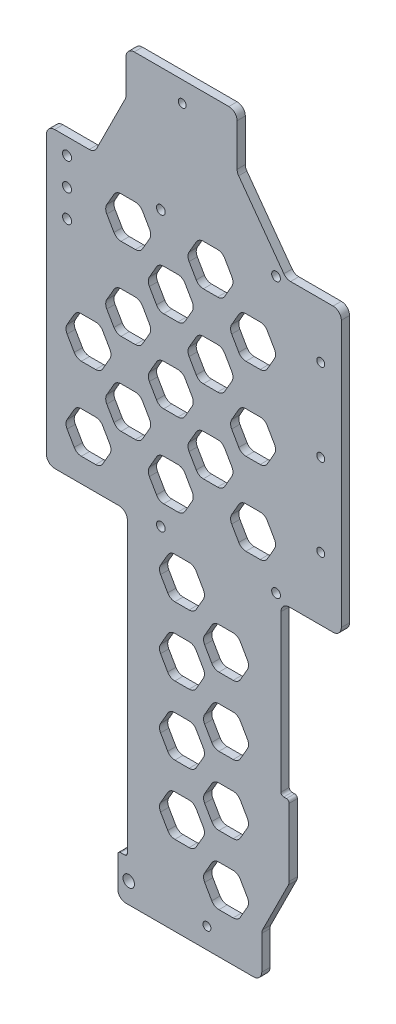
SolidWorks part; units mm, degrees
material "轻木"
ref_plane "前视基准面" through (0, 0, 0) normal (0, 0, 1) x (1, 0, 0)
ref_plane "上视基准面" through (0, 0, 0) normal (0, 1, 0) x (1, 0, 0)
ref_plane "右视基准面" through (0, 0, 0) normal (1, 0, 0) x (0, 0, -1)
other "Configuration Table"
sketch "草图1" plane through (0, 0, 0) normal (0, 0, 1) x (1, 0, 0)
  line L1 (260.5, -262.8015) -> (266.5, -262.8015)
  line L6 (266.5, -262.8015) -> (266.5, -247.8015)
  line L9 (266.5, -247.8015) -> (263, -247.8015) construction
  line L11 (260.5, -247.8015) -> (260.5, -188.5488) construction
  line L14 (307, -262.8015) -> (303.5, -262.8015)
  line L17 (303.5, -262.8015) -> (303.5, -247.8015)
  line L21 (303.5, -247.8015) -> (307, -247.8015)
  line L23 (307, -247.8015) -> (307, -188.5488)
  line L25 (266.5, -247.8015) -> (263, -247.8015)
  line L33 (263, -247.8015) -> (263, -138.5488)
  line L34 (263, -138.5488) -> (307, -138.5488)
  line L39 (219, 7.5) -> (267.5, 7.5) construction
  line L40 (219, 7.5) -> (219, -4.5) construction
  line L41 (267.5, 7.5) -> (267.5, -7.5) construction
  line L42 (570, -7.5) -> (0, -7.5) construction
  line L43 (267.5, -7.5) -> (277.5, -27.5) construction
  line L44 (277.5, -247.8015) -> (277.5, -7.5015) construction
  line L45 (277.5, -27.5) -> (292.5, -27.5) construction
  line L46 (292.5, -247.8015) -> (292.5, -7.5015) construction
  line L47 (292.5, -27.5) -> (302.5, -7.5) construction
  line L48 (302.5, -7.5) -> (302.5, 7.5) construction
  line L49 (570, 7.5) -> (0, 7.5) construction
  line L50 (302.5, 7.5) -> (351, 7.5) construction
  line L51 (351, 7.5) -> (351, -10.5) construction
  line L52 (351, -10.5) -> (367, -32.5) construction
  line L54 (367, -32.5) -> (367, -13.5) construction
  line L55 (373, -32.5) -> (367, -32.5) construction
  line L56 (367, -32.5) -> (385, -32.5) construction
  line L57 (388, -32.5) -> (382, -32.5) construction
  line L58 (385, -32.5) -> (385, -143.5) construction
  line L59 (385, -143.5) -> (367, -143.5) construction
  line L60 (367, -143.5) -> (367, -196.5) construction
  line L61 (367, -196.5) -> (370, -196.5) construction
  line L62 (370, -196.5) -> (370, -227.8015) construction
  line L63 (370, -7.5015) -> (370, -247.8015) construction
  line L64 (370, -227.8015) -> (360, -247.8015) construction
  line L65 (465, -247.8015) -> (105, -247.8015) construction
  line L66 (360, -247.8015) -> (360, -262.8015) construction
  line L67 (303, -262.8015) -> (303, -192.5488) construction
  line L68 (303, -192.5488) -> (264.5, -192.5488) construction
  line L69 (264.5, -192.5488) -> (264.5, -262.8015) construction
  line L70 (465, -262.8015) -> (105, -262.8015) construction
  line L71 (360, -262.8015) -> (303, -262.8015) construction
  line L72 (360.5279, -246.7458) -> (368.618, -230.5654) construction
  line L73 (264.5, -262.8015) -> (210, -262.8015) construction
  line L74 (210, -262.8015) -> (210, -247.8015) construction
  line L75 (210, -247.8015) -> (200, -227.8015) construction
  line L76 (200, -7.5015) -> (200, -247.8015) construction
  line L77 (200, -227.8015) -> (200, -196.5) construction
  line L78 (200, -196.5) -> (203, -196.5) construction
  line L79 (203, -196.5) -> (203, -143.5) construction
  line L80 (203, -143.5) -> (185, -143.5) construction
  line L81 (188, -143.5) -> (182, -143.5) construction
  line L82 (185, -143.5) -> (185, -32.5) construction
  line L83 (185, -7.5015) -> (185, -247.8015) construction
  line L84 (185, -32.5) -> (203, -32.5) construction
  line L85 (203, -32.5) -> (219, -10.5) construction
  line L86 (219, -10.5) -> (219, 7.5) construction
  line L87 (276.118, -24.7361) -> (268.0279, -8.5557) construction
  line L88 (301.9721, -8.5557) -> (293.882, -24.7361) construction
  line L89 (201.382, -230.5654) -> (209.4721, -246.7458) construction
  line L90 (223, -11.8007) -> (223, 3.5) construction
  line L91 (223, 3.5) -> (263.5, 3.5) construction
  line L92 (263.5, 3.5) -> (263.5, -8.4443) construction
  line L93 (263.5, -8.4443) -> (275.0279, -31.5) construction
  line L94 (275.0279, -31.5) -> (294.9721, -31.5) construction
  line L95 (294.9721, -31.5) -> (306.5, -8.4443) construction
  line L96 (306.5, -8.4443) -> (306.5, 3.5) construction
  line L97 (306.5, 3.5) -> (347, 3.5) construction
  line L98 (347, 3.5) -> (347, -11.8007) construction
  line L99 (347, -11.8007) -> (364.9631, -36.5) construction
  line L100 (364.9631, -36.5) -> (381, -36.5) construction
  line L101 (381, -36.5) -> (381, -139.5) construction
  line L102 (381, -139.5) -> (363, -139.5) construction
  line L103 (363, -139.5) -> (363, -200.5) construction
  line L104 (363, -200.5) -> (366, -200.5) construction
  line L105 (366, -200.5) -> (366, -226.8572) construction
  line L106 (366, -226.8572) -> (356, -246.8572) construction
  line L107 (356, -246.8572) -> (356, -258.8015) construction
  line L108 (356, -258.8015) -> (307, -258.8015) construction
  line L109 (307, -258.8015) -> (307, -188.5488) construction
  line L110 (307, -188.5488) -> (260.5, -188.5488) construction
  line L111 (260.5, -188.5488) -> (260.5, -258.8015) construction
  line L112 (260.5, -258.8015) -> (214, -258.8015) construction
  line L113 (214, -258.8015) -> (214, -246.8572) construction
  line L114 (214, -246.8572) -> (204, -226.8572) construction
  line L115 (204, -226.8572) -> (204, -200.5) construction
  line L116 (204, -200.5) -> (207, -200.5) construction
  line L117 (207, -200.5) -> (207, -139.5) construction
  line L118 (207, -139.5) -> (189, -139.5) construction
  line L119 (189, -139.5) -> (189, -36.5) construction
  line L120 (189, -36.5) -> (205.0369, -36.5) construction
  line L121 (205.0369, -36.5) -> (223, -11.8007) construction
  line L122 (223, -11.8007) -> (223, 7.5)
  line L123 (263.5, -8.4443) -> (263.5, 7.5)
  line L124 (263.5, 7.5) -> (223, 7.5)
  line L125 (223, -11.8007) -> (205.0369, -36.5)
  line L126 (205.0369, -36.5) -> (185, -36.5)
  line L127 (185, -36.5) -> (185, -139.5)
  line L128 (185, -139.5) -> (207, -139.5)
  line L129 (207, -139.5) -> (207, -200.5)
  line L130 (204, -200.5) -> (204, -226.8572)
  line L131 (204, -226.8572) -> (214, -246.8572)
  line L132 (204, -200.5) -> (207, -200.5)
  line L133 (214, -246.8572) -> (214, -262.8015)
  line L134 (214, -262.8015) -> (260.5, -262.8015)
  line L135 (260.5, -262.8015) -> (260.5, -188.5488) construction
  line L137 (307, -188.5488) -> (307, -262.8015) construction
  line L138 (307, -262.8015) -> (356, -262.8015)
  line L139 (356, -262.8015) -> (356, -246.8572)
  line L140 (356, -246.8572) -> (366, -226.8572)
  line L141 (366, -226.8572) -> (366, -200.5)
  line L142 (366, -200.5) -> (363, -200.5)
  line L143 (363, -200.5) -> (363, -139.5)
  line L144 (363, -139.5) -> (385, -139.5)
  line L145 (385, -139.5) -> (385, -36.5)
  line L146 (385, -36.5) -> (364.9631, -36.5)
  line L147 (364.9631, -36.5) -> (347, -11.8007)
  line L151 (306.5, -8.4443) -> (294.9721, -31.5)
  line L152 (294.9721, -31.5) -> (275.0279, -31.5)
  line L153 (275.0279, -31.5) -> (263.5, -8.4443)
  line L154 (306.5, -8.4443) -> (306.5, 7.5)
  line L155 (306.5, 7.5) -> (347, 7.5)
  line L156 (347, 7.5) -> (347, -11.8007)
  line L157 (260.5, -188.5488) -> (260.5, -138.5488) construction
  line L158 (260.5, -138.5488) -> (307, -138.5488) construction
  line L159 (307, -138.5488) -> (307, -188.5488)
  circle A0 centre (262.5, -255.3015) radius 2.1
  circle A1 centre (307.5, -255.3015) radius 2.1
  dimension "D7" = 7.5
  dimension "D8" = 7.5
  dimension "D9" = 4
  dimension "D11" = 4.2
  dimension "D12" = 4.2
  dimension "D2" = 50
  dimension "D3" = 15
  dimension "D4" = 15
  dimension "D5" = 6
  dimension "D6" = 3.5
  dimension "D10" = 0.5
  dimension "D13" = 3.5
  dimension "D1" = 4
extrude "凸台-拉伸1" add sketch "草图1" along normal blind 3
sketch "草图2" plane through (0, 0, 3) normal (0, 0, 1) x (1, 0, 0)
  line L0 (192.5, -27.4253) -> (192.5, -166.3023) construction
  line L1 (209.9028, 0) -> (386.3764, 0) construction
  line L3 (194.5573, -255.3015) -> (369.9095, -255.3015) construction
  line L4 (185, -36.5) -> (185, -139.5) construction
  line L5 (285, 13.2404) -> (285, -276.9819) construction
  line L6 (385, -139.5) -> (385, -36.5) construction
  line L7 (263.5, 7.5) -> (223, 7.5) construction
  line L8 (214, -262.8015) -> (266.5, -262.8015) construction
  line L9 (223, 7.5) -> (223, -11.8007) construction
  line L10 (205.0369, -36.5) -> (185, -36.5) construction
  line L11 (214, -246.8572) -> (214, -262.8015) construction
  circle A0 centre (192.5, -56.5) radius 1.45
  circle A1 centre (192.5, -86.5) radius 1.45
  circle A2 centre (192.5, -116.5) radius 1.45
  circle A3 centre (243, 0) radius 1.45
  circle A4 centre (234, -255.3015) radius 1.45
  circle A5 centre (377.5, -56.5) radius 1.45
  circle A6 centre (327, 0) radius 1.45
  circle A7 centre (377.5, -86.5) radius 1.45
  circle A8 centre (377.5, -116.5) radius 1.45
  circle A9 centre (336, -255.3015) radius 1.45
  dimension "D5" = 20
  dimension "D6" = 30
  dimension "D7" = 30
  dimension "D8" = 2.9
  dimension "D1" = 7.5
  dimension "D2" = 7.5
  dimension "D3" = 7.5
  dimension "D4" = 20
  dimension "D9" = 20
extrude "切除-拉伸1" cut sketch "草图2" against normal through all
fillet "圆角2" radius 3 28 edges at (214, -262.8015, 1.5) (214, -246.8572, 1.5) (204, -226.8572, 1.5) (207, -139.5, 1.5) (185, -139.5, 1.5) (185, -36.5, 1.5) (205.0369, -36.5, 1.5) (223, -11.8007, 1.5) (223, 7.5, 1.5) (263.5, 7.5, 1.5) (263.5, -8.4443, 1.5) (275.0279, -31.5, 1.5) (294.9721, -31.5, 1.5) (306.5, -8.4443, 1.5) (306.5, 7.5, 1.5) (347, 7.5, 1.5) (385, -36.5, 1.5) (385, -139.5, 1.5) (363, -139.5, 1.5) (366, -226.8572, 1.5) (356, -246.8572, 1.5) (356, -262.8015, 1.5) (347, -11.8007, 1.5) (364.9631, -36.5, 1.5) (303.5, -262.8015, 1.5) (266.5, -262.8015, 1.5) (307, -138.5488, 1.5) (263, -138.5488, 1.5)
fillet "圆角4" radius 1 8 edges at (204, -200.5, 1.5) (207, -200.5, 1.5) (366, -200.5, 1.5) (363, -200.5, 1.5) (307, -247.8015, 1.5) (303.5, -247.8015, 1.5) (263, -247.8015, 1.5) (266.5, -247.8015, 1.5)
sketch "草图3" plane through (0, 0, 3) normal (0, 0, 1) x (1, 0, 0)
  circle A0 centre (319.2014, -37.5) radius 1.6 construction
  circle A1 centre (361.2014, -37.5) radius 1.6 construction
  circle A2 centre (319.2014, -37.5) radius 1.6
  circle A3 centre (361.2014, -37.5) radius 1.6
  circle A4 centre (361.2014, -137.5) radius 1.6 construction
  circle A5 centre (319.2014, -137.5) radius 1.6 construction
  circle A6 centre (361.2014, -137.5) radius 1.6
  circle A7 centre (319.2014, -137.5) radius 1.6
  circle A8 centre (285, -37.5) radius 1.65 construction
  circle A9 centre (285, -47.5) radius 1.65 construction
  circle A10 centre (285, -57.5) radius 1.65 construction
  circle A11 centre (285, -37.5) radius 1.65
  circle A12 centre (285, -47.5) radius 1.65
  circle A13 centre (285, -57.5) radius 1.65
extrude "切除-拉伸2" cut sketch "草图3" against normal through all
sketch "草图4" plane through (0, 0, 3) normal (0, 0, 1) x (1, 0, 0)
  line L0 (255.9607, -47.2012) -> (251.6306, -39.7012)
  line L1 (225.9607, -47.2012) -> (221.6306, -39.7012)
  line L2 (221.6306, -39.7012) -> (212.9703, -39.7012)
  line L3 (212.9703, -39.7012) -> (208.6402, -47.2012)
  line L4 (208.6402, -47.2012) -> (212.9703, -54.7012)
  line L5 (212.9703, -54.7012) -> (221.6306, -54.7012)
  line L6 (221.6306, -54.7012) -> (225.9607, -47.2012)
  line L7 (241.4816, -62.3181) -> (237.1515, -54.8181)
  line L8 (237.1515, -54.8181) -> (228.4912, -54.8181)
  line L9 (228.4912, -54.8181) -> (224.1611, -62.3181)
  line L10 (224.1611, -62.3181) -> (228.4912, -69.8181)
  line L11 (228.4912, -69.8181) -> (237.1515, -69.8181)
  line L12 (237.1515, -69.8181) -> (241.4816, -62.3181)
  line L13 (251.6306, -39.7012) -> (242.9703, -39.7012)
  line L14 (242.9703, -39.7012) -> (238.6402, -47.2012)
  line L15 (238.6402, -47.2012) -> (242.9703, -54.7012)
  line L16 (242.9703, -54.7012) -> (251.6306, -54.7012)
  line L17 (251.6306, -54.7012) -> (255.9607, -47.2012)
  line L18 (271.4816, -62.3181) -> (267.1515, -54.8181)
  line L19 (267.1515, -54.8181) -> (258.4912, -54.8181)
  line L20 (258.4912, -54.8181) -> (254.1611, -62.3181)
  line L21 (254.1611, -62.3181) -> (258.4912, -69.8181)
  line L22 (258.4912, -69.8181) -> (267.1515, -69.8181)
  line L23 (267.1515, -69.8181) -> (271.4816, -62.3181)
  line L36 (315.9607, -47.2012) -> (311.6306, -39.7012)
  line L37 (311.6306, -39.7012) -> (302.9703, -39.7012)
  line L38 (302.9703, -39.7012) -> (298.6402, -47.2012)
  line L39 (298.6402, -47.2012) -> (302.9703, -54.7012)
  line L40 (302.9703, -54.7012) -> (311.6306, -54.7012)
  line L41 (311.6306, -54.7012) -> (315.9607, -47.2012)
  line L42 (331.4816, -62.3181) -> (327.1515, -54.8181)
  line L43 (327.1515, -54.8181) -> (318.4912, -54.8181)
  line L44 (318.4912, -54.8181) -> (314.1611, -62.3181)
  line L45 (314.1611, -62.3181) -> (318.4912, -69.8181)
  line L46 (318.4912, -69.8181) -> (327.1515, -69.8181)
  line L47 (327.1515, -69.8181) -> (331.4816, -62.3181)
  line L48 (345.9607, -47.2012) -> (341.6306, -39.7012)
  line L49 (341.6306, -39.7012) -> (332.9703, -39.7012)
  line L50 (332.9703, -39.7012) -> (328.6402, -47.2012)
  line L51 (328.6402, -47.2012) -> (332.9703, -54.7012)
  line L52 (332.9703, -54.7012) -> (341.6306, -54.7012)
  line L53 (341.6306, -54.7012) -> (345.9607, -47.2012)
  line L54 (361.4816, -62.3181) -> (357.1515, -54.8181)
  line L55 (357.1515, -54.8181) -> (348.4912, -54.8181)
  line L56 (348.4912, -54.8181) -> (344.1611, -62.3181)
  line L57 (344.1611, -62.3181) -> (348.4912, -69.8181)
  line L58 (348.4912, -69.8181) -> (357.1515, -69.8181)
  line L59 (357.1515, -69.8181) -> (361.4816, -62.3181)
  line L60 (255.9607, -77.2012) -> (251.6306, -69.7012)
  line L61 (251.6306, -69.7012) -> (242.9703, -69.7012)
  line L62 (242.9703, -69.7012) -> (238.6402, -77.2012)
  line L63 (238.6402, -77.2012) -> (242.9703, -84.7012)
  line L64 (242.9703, -84.7012) -> (251.6306, -84.7012)
  line L65 (251.6306, -84.7012) -> (255.9607, -77.2012)
  line L66 (271.4816, -92.3181) -> (267.1515, -84.8181)
  line L67 (267.1515, -84.8181) -> (258.4912, -84.8181)
  line L68 (258.4912, -84.8181) -> (254.1611, -92.3181)
  line L69 (254.1611, -92.3181) -> (258.4912, -99.8181)
  line L70 (258.4912, -99.8181) -> (267.1515, -99.8181)
  line L71 (267.1515, -99.8181) -> (271.4816, -92.3181)
  line L78 (301.4816, -92.3181) -> (297.1515, -84.8181)
  line L79 (297.1515, -84.8181) -> (288.4912, -84.8181)
  line L80 (288.4912, -84.8181) -> (284.1611, -92.3181)
  line L81 (284.1611, -92.3181) -> (288.4912, -99.8181)
  line L82 (288.4912, -99.8181) -> (297.1515, -99.8181)
  line L83 (297.1515, -99.8181) -> (301.4816, -92.3181)
  line L84 (315.9607, -77.2012) -> (311.6306, -69.7012)
  line L85 (311.6306, -69.7012) -> (302.9703, -69.7012)
  line L86 (302.9703, -69.7012) -> (298.6402, -77.2012)
  line L87 (298.6402, -77.2012) -> (302.9703, -84.7012)
  line L88 (302.9703, -84.7012) -> (311.6306, -84.7012)
  line L89 (311.6306, -84.7012) -> (315.9607, -77.2012)
  line L90 (331.4816, -92.3181) -> (327.1515, -84.8181)
  line L91 (327.1515, -84.8181) -> (318.4912, -84.8181)
  line L92 (318.4912, -84.8181) -> (314.1611, -92.3181)
  line L93 (314.1611, -92.3181) -> (318.4912, -99.8181)
  line L94 (318.4912, -99.8181) -> (327.1515, -99.8181)
  line L95 (327.1515, -99.8181) -> (331.4816, -92.3181)
  line L96 (345.9607, -77.2012) -> (341.6306, -69.7012)
  line L97 (341.6306, -69.7012) -> (332.9703, -69.7012)
  line L98 (332.9703, -69.7012) -> (328.6402, -77.2012)
  line L99 (328.6402, -77.2012) -> (332.9703, -84.7012)
  line L100 (332.9703, -84.7012) -> (341.6306, -84.7012)
  line L101 (341.6306, -84.7012) -> (345.9607, -77.2012)
  line L102 (361.4816, -92.3181) -> (357.1515, -84.8181)
  line L103 (357.1515, -84.8181) -> (348.4912, -84.8181)
  line L104 (348.4912, -84.8181) -> (344.1611, -92.3181)
  line L105 (344.1611, -92.3181) -> (348.4912, -99.8181)
  line L106 (348.4912, -99.8181) -> (357.1515, -99.8181)
  line L107 (357.1515, -99.8181) -> (361.4816, -92.3181)
  line L108 (255.9607, -107.2012) -> (251.6306, -99.7012)
  line L109 (251.6306, -99.7012) -> (242.9703, -99.7012)
  line L110 (242.9703, -99.7012) -> (238.6402, -107.2012)
  line L111 (238.6402, -107.2012) -> (242.9703, -114.7012)
  line L112 (242.9703, -114.7012) -> (251.6306, -114.7012)
  line L113 (251.6306, -114.7012) -> (255.9607, -107.2012)
  line L114 (271.4816, -122.3181) -> (267.1515, -114.8181)
  line L115 (267.1515, -114.8181) -> (258.4912, -114.8181)
  line L116 (258.4912, -114.8181) -> (254.1611, -122.3181)
  line L117 (254.1611, -122.3181) -> (258.4912, -129.8181)
  line L118 (258.4912, -129.8181) -> (267.1515, -129.8181)
  line L119 (267.1515, -129.8181) -> (271.4816, -122.3181)
  line L126 (301.4816, -122.3181) -> (297.1515, -114.8181)
  line L127 (297.1515, -114.8181) -> (288.4912, -114.8181)
  line L128 (288.4912, -114.8181) -> (284.1611, -122.3181)
  line L129 (284.1611, -122.3181) -> (288.4912, -129.8181)
  line L130 (288.4912, -129.8181) -> (297.1515, -129.8181)
  line L131 (297.1515, -129.8181) -> (301.4816, -122.3181)
  line L132 (315.9607, -107.2012) -> (311.6306, -99.7012)
  line L133 (311.6306, -99.7012) -> (302.9703, -99.7012)
  line L134 (302.9703, -99.7012) -> (298.6402, -107.2012)
  line L135 (298.6402, -107.2012) -> (302.9703, -114.7012)
  line L136 (302.9703, -114.7012) -> (311.6306, -114.7012)
  line L137 (311.6306, -114.7012) -> (315.9607, -107.2012)
  line L138 (331.4816, -122.3181) -> (327.1515, -114.8181)
  line L139 (327.1515, -114.8181) -> (318.4912, -114.8181)
  line L140 (318.4912, -114.8181) -> (314.1611, -122.3181)
  line L141 (314.1611, -122.3181) -> (318.4912, -129.8181)
  line L142 (318.4912, -129.8181) -> (327.1515, -129.8181)
  line L143 (327.1515, -129.8181) -> (331.4816, -122.3181)
  line L144 (345.9607, -107.2012) -> (341.6306, -99.7012)
  line L145 (341.6306, -99.7012) -> (332.9703, -99.7012)
  line L146 (332.9703, -99.7012) -> (328.6402, -107.2012)
  line L147 (328.6402, -107.2012) -> (332.9703, -114.7012)
  line L148 (332.9703, -114.7012) -> (341.6306, -114.7012)
  line L149 (341.6306, -114.7012) -> (345.9607, -107.2012)
  line L150 (361.4816, -122.3181) -> (357.1515, -114.8181)
  line L151 (357.1515, -114.8181) -> (348.4912, -114.8181)
  line L152 (348.4912, -114.8181) -> (344.1611, -122.3181)
  line L153 (344.1611, -122.3181) -> (348.4912, -129.8181)
  line L154 (348.4912, -129.8181) -> (357.1515, -129.8181)
  line L155 (357.1515, -129.8181) -> (361.4816, -122.3181)
  line L156 (225.9607, -77.2012) -> (221.6306, -69.7012)
  line L157 (221.6306, -69.7012) -> (212.9703, -69.7012)
  line L158 (212.9703, -69.7012) -> (208.6402, -77.2012)
  line L159 (208.6402, -77.2012) -> (212.9703, -84.7012)
  line L160 (212.9703, -84.7012) -> (221.6306, -84.7012)
  line L161 (221.6306, -84.7012) -> (225.9607, -77.2012)
  line L162 (241.4816, -92.3181) -> (237.1515, -84.8181)
  line L163 (237.1515, -84.8181) -> (228.4912, -84.8181)
  line L164 (228.4912, -84.8181) -> (224.1611, -92.3181)
  line L165 (224.1611, -92.3181) -> (228.4912, -99.8181)
  line L166 (228.4912, -99.8181) -> (237.1515, -99.8181)
  line L167 (237.1515, -99.8181) -> (241.4816, -92.3181)
  line L168 (225.9607, -107.2012) -> (221.6306, -99.7012)
  line L169 (221.6306, -99.7012) -> (212.9703, -99.7012)
  line L170 (212.9703, -99.7012) -> (208.6402, -107.2012)
  line L171 (208.6402, -107.2012) -> (212.9703, -114.7012)
  line L172 (212.9703, -114.7012) -> (221.6306, -114.7012)
  line L173 (221.6306, -114.7012) -> (225.9607, -107.2012)
  line L174 (241.4816, -122.3181) -> (237.1515, -114.8181)
  line L175 (237.1515, -114.8181) -> (228.4912, -114.8181)
  line L176 (228.4912, -114.8181) -> (224.1611, -122.3181)
  line L177 (224.1611, -122.3181) -> (228.4912, -129.8181)
  line L178 (228.4912, -129.8181) -> (237.1515, -129.8181)
  line L179 (237.1515, -129.8181) -> (241.4816, -122.3181)
  line L180 (335.5655, -151.2096) -> (331.2354, -143.7096)
  line L181 (235.5655, -151.2096) -> (231.2354, -143.7096)
  line L182 (231.2354, -143.7096) -> (222.5752, -143.7096)
  line L183 (222.5752, -143.7096) -> (218.245, -151.2096)
  line L184 (218.245, -151.2096) -> (222.5752, -158.7096)
  line L185 (222.5752, -158.7096) -> (231.2354, -158.7096)
  line L186 (231.2354, -158.7096) -> (235.5655, -151.2096)
  line L187 (251.6306, -165.3842) -> (247.3004, -157.8842)
  line L188 (247.3004, -157.8842) -> (238.6402, -157.8842)
  line L189 (238.6402, -157.8842) -> (234.3101, -165.3842)
  line L190 (234.3101, -165.3842) -> (238.6402, -172.8842)
  line L191 (238.6402, -172.8842) -> (247.3004, -172.8842)
  line L192 (247.3004, -172.8842) -> (251.6306, -165.3842)
  line L193 (331.2354, -143.7096) -> (322.5752, -143.7096)
  line L194 (322.5752, -143.7096) -> (318.245, -151.2096)
  line L195 (318.245, -151.2096) -> (322.5752, -158.7096)
  line L196 (322.5752, -158.7096) -> (331.2354, -158.7096)
  line L197 (331.2354, -158.7096) -> (335.5655, -151.2096)
  line L198 (351.6306, -165.3842) -> (347.3004, -157.8842)
  line L199 (347.3004, -157.8842) -> (338.6402, -157.8842)
  line L200 (338.6402, -157.8842) -> (334.3101, -165.3842)
  line L201 (334.3101, -165.3842) -> (338.6402, -172.8842)
  line L202 (338.6402, -172.8842) -> (347.3004, -172.8842)
  line L203 (347.3004, -172.8842) -> (351.6306, -165.3842)
  line L204 (335.5655, -176.2096) -> (331.2354, -168.7096)
  line L205 (331.2354, -168.7096) -> (322.5752, -168.7096)
  line L206 (322.5752, -168.7096) -> (318.245, -176.2096)
  line L207 (318.245, -176.2096) -> (322.5752, -183.7096)
  line L208 (322.5752, -183.7096) -> (331.2354, -183.7096)
  line L209 (331.2354, -183.7096) -> (335.5655, -176.2096)
  line L210 (351.6306, -190.3842) -> (347.3004, -182.8842)
  line L211 (347.3004, -182.8842) -> (338.6402, -182.8842)
  line L212 (338.6402, -182.8842) -> (334.3101, -190.3842)
  line L213 (334.3101, -190.3842) -> (338.6402, -197.8842)
  line L214 (338.6402, -197.8842) -> (347.3004, -197.8842)
  line L215 (347.3004, -197.8842) -> (351.6306, -190.3842)
  line L216 (335.5655, -201.2096) -> (331.2354, -193.7096)
  line L217 (331.2354, -193.7096) -> (322.5752, -193.7096)
  line L218 (322.5752, -193.7096) -> (318.245, -201.2096)
  line L219 (318.245, -201.2096) -> (322.5752, -208.7096)
  line L220 (322.5752, -208.7096) -> (331.2354, -208.7096)
  line L221 (331.2354, -208.7096) -> (335.5655, -201.2096)
  line L222 (351.6306, -215.3842) -> (347.3004, -207.8842)
  line L223 (347.3004, -207.8842) -> (338.6402, -207.8842)
  line L224 (338.6402, -207.8842) -> (334.3101, -215.3842)
  line L225 (334.3101, -215.3842) -> (338.6402, -222.8842)
  line L226 (338.6402, -222.8842) -> (347.3004, -222.8842)
  line L227 (347.3004, -222.8842) -> (351.6306, -215.3842)
  line L228 (335.5655, -226.2096) -> (331.2354, -218.7096)
  line L229 (331.2354, -218.7096) -> (322.5752, -218.7096)
  line L230 (322.5752, -218.7096) -> (318.245, -226.2096)
  line L231 (318.245, -226.2096) -> (322.5752, -233.7096)
  line L232 (322.5752, -233.7096) -> (331.2354, -233.7096)
  line L233 (331.2354, -233.7096) -> (335.5655, -226.2096)
  line L234 (351.6306, -240.3842) -> (347.3004, -232.8842)
  line L235 (347.3004, -232.8842) -> (338.6402, -232.8842)
  line L236 (338.6402, -232.8842) -> (334.3101, -240.3842)
  line L237 (334.3101, -240.3842) -> (338.6402, -247.8842)
  line L238 (338.6402, -247.8842) -> (347.3004, -247.8842)
  line L239 (347.3004, -247.8842) -> (351.6306, -240.3842)
  line L240 (235.5655, -176.2096) -> (231.2354, -168.7096)
  line L241 (231.2354, -168.7096) -> (222.5752, -168.7096)
  line L242 (222.5752, -168.7096) -> (218.245, -176.2096)
  line L243 (218.245, -176.2096) -> (222.5752, -183.7096)
  line L244 (222.5752, -183.7096) -> (231.2354, -183.7096)
  line L245 (231.2354, -183.7096) -> (235.5655, -176.2096)
  line L246 (251.6306, -190.3842) -> (247.3004, -182.8842)
  line L247 (247.3004, -182.8842) -> (238.6402, -182.8842)
  line L248 (238.6402, -182.8842) -> (234.3101, -190.3842)
  line L249 (234.3101, -190.3842) -> (238.6402, -197.8842)
  line L250 (238.6402, -197.8842) -> (247.3004, -197.8842)
  line L251 (247.3004, -197.8842) -> (251.6306, -190.3842)
  line L252 (235.5655, -201.2096) -> (231.2354, -193.7096)
  line L253 (231.2354, -193.7096) -> (222.5752, -193.7096)
  line L254 (222.5752, -193.7096) -> (218.245, -201.2096)
  line L255 (218.245, -201.2096) -> (222.5752, -208.7096)
  line L256 (222.5752, -208.7096) -> (231.2354, -208.7096)
  line L257 (231.2354, -208.7096) -> (235.5655, -201.2096)
  line L258 (251.6306, -215.3842) -> (247.3004, -207.8842)
  line L259 (247.3004, -207.8842) -> (238.6402, -207.8842)
  line L260 (238.6402, -207.8842) -> (234.3101, -215.3842)
  line L261 (234.3101, -215.3842) -> (238.6402, -222.8842)
  line L262 (238.6402, -222.8842) -> (247.3004, -222.8842)
  line L263 (247.3004, -222.8842) -> (251.6306, -215.3842)
  line L264 (235.5655, -226.2096) -> (231.2354, -218.7096)
  line L265 (231.2354, -218.7096) -> (222.5752, -218.7096)
  line L266 (222.5752, -218.7096) -> (218.245, -226.2096)
  line L267 (218.245, -226.2096) -> (222.5752, -233.7096)
  line L268 (222.5752, -233.7096) -> (231.2354, -233.7096)
  line L269 (231.2354, -233.7096) -> (235.5655, -226.2096)
  line L270 (251.6306, -240.3842) -> (247.3004, -232.8842)
  line L271 (247.3004, -232.8842) -> (238.6402, -232.8842)
  line L272 (238.6402, -232.8842) -> (234.3101, -240.3842)
  line L273 (234.3101, -240.3842) -> (238.6402, -247.8842)
  line L274 (238.6402, -247.8842) -> (247.3004, -247.8842)
  line L275 (247.3004, -247.8842) -> (251.6306, -240.3842)
  line L276 (272.9703, -39.7012) -> (268.6402, -47.2012) [skipped]
  line L277 (272.9703, -54.7012) -> (281.6306, -54.7012) [skipped]
  line L278 (268.6402, -47.2012) -> (272.9703, -54.7012) [skipped]
  line L279 (281.6306, -54.7012) -> (285.9607, -47.2012) [skipped]
  line L280 (285.9607, -47.2012) -> (281.6306, -39.7012) [skipped]
  line L281 (281.6306, -39.7012) -> (272.9703, -39.7012) [skipped]
  line L282 (288.4912, -54.8181) -> (284.1611, -62.3181) [skipped]
  line L283 (284.1611, -62.3181) -> (288.4912, -69.8181) [skipped]
  line L284 (288.4912, -69.8181) -> (297.1515, -69.8181) [skipped]
  line L285 (297.1515, -69.8181) -> (301.4816, -62.3181) [skipped]
  line L286 (301.4816, -62.3181) -> (297.1515, -54.8181) [skipped]
  line L287 (297.1515, -54.8181) -> (288.4912, -54.8181) [skipped]
  line L288 (281.6306, -69.7012) -> (272.9703, -69.7012) [skipped]
  line L289 (272.9703, -84.7012) -> (281.6306, -84.7012) [skipped]
  line L290 (281.6306, -99.7012) -> (272.9703, -99.7012) [skipped]
  line L291 (272.9703, -114.7012) -> (281.6306, -114.7012) [skipped]
  line L292 (281.6306, -114.7012) -> (285.9607, -107.2012) [skipped]
  line L293 (285.9607, -107.2012) -> (281.6306, -99.7012) [skipped]
  line L294 (268.6402, -107.2012) -> (272.9703, -114.7012) [skipped]
  line L295 (272.9703, -99.7012) -> (268.6402, -107.2012) [skipped]
  line L296 (285.9607, -77.2012) -> (281.6306, -69.7012) [skipped]
  line L297 (281.6306, -84.7012) -> (285.9607, -77.2012) [skipped]
  line L298 (272.9703, -69.7012) -> (268.6402, -77.2012) [skipped]
  line L299 (268.6402, -77.2012) -> (272.9703, -84.7012) [skipped]
  circle A0 centre (217.3004, -47.2012) radius 7.5 construction
  circle A1 centre (232.8214, -62.3181) radius 7.5 construction
  circle A2 centre (226.9053, -151.2096) radius 7.5 construction
  circle A3 centre (242.9703, -165.3842) radius 7.5 construction
  dimension "D2" = 15
  dimension "D3" = 15
  dimension "D7" = 15
  dimension "D8" = 15
  dimension "D1" = 6
  dimension "D6" = 6
  dimension "D4" = 5
  dimension "D5" = 3
  dimension "D9" = 2
  dimension "D10" = 4
extrude "切除-拉伸3" cut sketch "草图4" against normal through all
fillet "圆角5" radius 3 252 edges at (221.6306, -54.7012, 1.5) (212.9703, -54.7012, 1.5) (208.6402, -47.2012, 1.5) (225.9607, -47.2012, 1.5) (347.3004, -247.8842, 1.5) (338.6402, -247.8842, 1.5) (334.3101, -240.3842, 1.5) (338.6402, -232.8842, 1.5) (347.3004, -232.8842, 1.5) (351.6306, -240.3842, 1.5) (231.2354, -183.7096, 1.5) (222.5752, -183.7096, 1.5) (218.245, -176.2096, 1.5) (222.5752, -168.7096, 1.5) (231.2354, -168.7096, 1.5) (235.5655, -176.2096, 1.5) (231.2354, -208.7096, 1.5) (222.5752, -208.7096, 1.5) (218.245, -201.2096, 1.5) (222.5752, -193.7096, 1.5) (231.2354, -193.7096, 1.5) (235.5655, -201.2096, 1.5) (247.3004, -197.8842, 1.5) (238.6402, -197.8842, 1.5) (234.3101, -190.3842, 1.5) (238.6402, -182.8842, 1.5) (247.3004, -182.8842, 1.5) (251.6306, -190.3842, 1.5) (331.2354, -208.7096, 1.5) (322.5752, -208.7096, 1.5) (318.245, -201.2096, 1.5) (322.5752, -193.7096, 1.5) (331.2354, -193.7096, 1.5) (335.5655, -201.2096, 1.5) (347.3004, -197.8842, 1.5) (338.6402, -197.8842, 1.5) (334.3101, -190.3842, 1.5) (338.6402, -182.8842, 1.5) (347.3004, -182.8842, 1.5) (351.6306, -190.3842, 1.5) (331.2354, -233.7096, 1.5) (322.5752, -233.7096, 1.5) (318.245, -226.2096, 1.5) (322.5752, -218.7096, 1.5) (331.2354, -218.7096, 1.5) (335.5655, -226.2096, 1.5) (347.3004, -222.8842, 1.5) (338.6402, -222.8842, 1.5) (334.3101, -215.3842, 1.5) (338.6402, -207.8842, 1.5) (347.3004, -207.8842, 1.5) (351.6306, -215.3842, 1.5) (247.3004, -247.8842, 1.5) (238.6402, -247.8842, 1.5) (234.3101, -240.3842, 1.5) (238.6402, -232.8842, 1.5) (247.3004, -232.8842, 1.5) (251.6306, -240.3842, 1.5) (247.3004, -222.8842, 1.5) (238.6402, -222.8842, 1.5) (234.3101, -215.3842, 1.5) (238.6402, -207.8842, 1.5) (247.3004, -207.8842, 1.5) (251.6306, -215.3842, 1.5) (231.2354, -233.7096, 1.5) (222.5752, -233.7096, 1.5) (218.245, -226.2096, 1.5) (222.5752, -218.7096, 1.5) (231.2354, -218.7096, 1.5) (235.5655, -226.2096, 1.5) (311.6306, -84.7012, 1.5) (302.9703, -84.7012, 1.5) (298.6402, -77.2012, 1.5) (302.9703, -69.7012, 1.5) (311.6306, -69.7012, 1.5) (315.9607, -77.2012, 1.5) (297.1515, -99.8181, 1.5) (288.4912, -99.8181, 1.5) (284.1611, -92.3181, 1.5) (288.4912, -84.8181, 1.5) (297.1515, -84.8181, 1.5) (301.4816, -92.3181, 1.5) (267.1515, -99.8181, 1.5) (258.4912, -99.8181, 1.5) (254.1611, -92.3181, 1.5) (258.4912, -84.8181, 1.5) (267.1515, -84.8181, 1.5) (271.4816, -92.3181, 1.5) (251.6306, -114.7012, 1.5) (242.9703, -114.7012, 1.5) (238.6402, -107.2012, 1.5) (242.9703, -99.7012, 1.5) (251.6306, -99.7012, 1.5) (255.9607, -107.2012, 1.5) (357.1515, -99.8181, 1.5) (348.4912, -99.8181, 1.5) (344.1611, -92.3181, 1.5) (348.4912, -84.8181, 1.5) (357.1515, -84.8181, 1.5) (361.4816, -92.3181, 1.5) (341.6306, -84.7012, 1.5) (332.9703, -84.7012, 1.5) (328.6402, -77.2012, 1.5) (332.9703, -69.7012, 1.5) (341.6306, -69.7012, 1.5) (345.9607, -77.2012, 1.5) (327.1515, -99.8181, 1.5) (318.4912, -99.8181, 1.5) (314.1611, -92.3181, 1.5) (318.4912, -84.8181, 1.5) (327.1515, -84.8181, 1.5) (331.4816, -92.3181, 1.5) (311.6306, -54.7012, 1.5) (302.9703, -54.7012, 1.5) (298.6402, -47.2012, 1.5) (302.9703, -39.7012, 1.5) (311.6306, -39.7012, 1.5) (315.9607, -47.2012, 1.5) (267.1515, -69.8181, 1.5) (258.4912, -69.8181, 1.5) (254.1611, -62.3181, 1.5) (258.4912, -54.8181, 1.5) (267.1515, -54.8181, 1.5) (271.4816, -62.3181, 1.5) (237.1515, -69.8181, 1.5) (228.4912, -69.8181, 1.5) (224.1611, -62.3181, 1.5) (228.4912, -54.8181, 1.5) (237.1515, -54.8181, 1.5) (241.4816, -62.3181, 1.5) (251.6306, -54.7012, 1.5) (242.9703, -54.7012, 1.5) (238.6402, -47.2012, 1.5) (242.9703, -39.7012, 1.5) (251.6306, -39.7012, 1.5) (255.9607, -47.2012, 1.5) (251.6306, -84.7012, 1.5) (242.9703, -84.7012, 1.5) (238.6402, -77.2012, 1.5) (242.9703, -69.7012, 1.5) (251.6306, -69.7012, 1.5) (255.9607, -77.2012, 1.5) (357.1515, -69.8181, 1.5) (348.4912, -69.8181, 1.5) (344.1611, -62.3181, 1.5) (348.4912, -54.8181, 1.5) (357.1515, -54.8181, 1.5) (361.4816, -62.3181, 1.5) (341.6306, -54.7012, 1.5) (332.9703, -54.7012, 1.5) (328.6402, -47.2012, 1.5) (332.9703, -39.7012, 1.5) (341.6306, -39.7012, 1.5) (345.9607, -47.2012, 1.5) (327.1515, -69.8181, 1.5) (318.4912, -69.8181, 1.5) (314.1611, -62.3181, 1.5) (318.4912, -54.8181, 1.5) (327.1515, -54.8181, 1.5) (331.4816, -62.3181, 1.5) (221.6306, -114.7012, 1.5) (212.9703, -114.7012, 1.5) (208.6402, -107.2012, 1.5) (212.9703, -99.7012, 1.5) (221.6306, -99.7012, 1.5) (225.9607, -107.2012, 1.5) (237.1515, -99.8181, 1.5) (228.4912, -99.8181, 1.5) (224.1611, -92.3181, 1.5) (228.4912, -84.8181, 1.5) (237.1515, -84.8181, 1.5) (241.4816, -92.3181, 1.5) (237.1515, -129.8181, 1.5) (228.4912, -129.8181, 1.5) (224.1611, -122.3181, 1.5) (228.4912, -114.8181, 1.5) (237.1515, -114.8181, 1.5) (241.4816, -122.3181, 1.5) (231.2354, -158.7096, 1.5) (222.5752, -158.7096, 1.5) (218.245, -151.2096, 1.5) (222.5752, -143.7096, 1.5) (231.2354, -143.7096, 1.5) (235.5655, -151.2096, 1.5) (347.3004, -172.8842, 1.5) (338.6402, -172.8842, 1.5) (334.3101, -165.3842, 1.5) (338.6402, -157.8842, 1.5) (347.3004, -157.8842, 1.5) (351.6306, -165.3842, 1.5) (331.2354, -183.7096, 1.5) (322.5752, -183.7096, 1.5) (318.245, -176.2096, 1.5) (322.5752, -168.7096, 1.5) (331.2354, -168.7096, 1.5) (335.5655, -176.2096, 1.5) (247.3004, -172.8842, 1.5) (238.6402, -172.8842, 1.5) (234.3101, -165.3842, 1.5) (238.6402, -157.8842, 1.5) (247.3004, -157.8842, 1.5) (251.6306, -165.3842, 1.5) (331.2354, -158.7096, 1.5) (322.5752, -158.7096, 1.5) (318.245, -151.2096, 1.5) (322.5752, -143.7096, 1.5) (331.2354, -143.7096, 1.5) (335.5655, -151.2096, 1.5) (311.6306, -114.7012, 1.5) (302.9703, -114.7012, 1.5) (298.6402, -107.2012, 1.5) (302.9703, -99.7012, 1.5) (311.6306, -99.7012, 1.5) (315.9607, -107.2012, 1.5) (297.1515, -129.8181, 1.5) (288.4912, -129.8181, 1.5) (284.1611, -122.3181, 1.5) (288.4912, -114.8181, 1.5) (297.1515, -114.8181, 1.5) (301.4816, -122.3181, 1.5) (267.1515, -129.8181, 1.5) (258.4912, -129.8181, 1.5) (254.1611, -122.3181, 1.5) (258.4912, -114.8181, 1.5) (267.1515, -114.8181, 1.5) (271.4816, -122.3181, 1.5) (221.6306, -84.7012, 1.5) (212.9703, -84.7012, 1.5) (208.6402, -77.2012, 1.5) (212.9703, -69.7012, 1.5) (221.6306, -69.7012, 1.5) (225.9607, -77.2012, 1.5) (357.1515, -129.8181, 1.5) (348.4912, -129.8181, 1.5) (344.1611, -122.3181, 1.5) (348.4912, -114.8181, 1.5) (357.1515, -114.8181, 1.5) (361.4816, -122.3181, 1.5) (341.6306, -114.7012, 1.5) (332.9703, -114.7012, 1.5) (328.6402, -107.2012, 1.5) (332.9703, -99.7012, 1.5) (341.6306, -99.7012, 1.5) (345.9607, -107.2012, 1.5) (327.1515, -129.8181, 1.5) (318.4912, -129.8181, 1.5) (314.1611, -122.3181, 1.5) (318.4912, -114.8181, 1.5) (327.1515, -114.8181, 1.5) (331.4816, -122.3181, 1.5) (221.6306, -39.7012, 1.5) (212.9703, -39.7012, 1.5)
sketch "草图6" plane through (0, 0, 3) normal (0, 0, 1) x (1, 0, 0)
  line L1 (174.1095, 13.8158) -> (277.5, 13.8158)
  line L2 (174.1095, 13.8158) -> (174.1095, -270.2682)
  line L3 (174.1095, -270.2682) -> (277.5, -270.2682)
  line L4 (277.5, 13.8158) -> (277.5, -270.2682)
  circle A0 centre (285, -37.5) radius 1.65 construction
  dimension "D1" = 7.5
extrude "切除-拉伸5" cut sketch "草图6" against normal through all
fillet "圆角7" radius 3 2 edges at (277.5, -138.5488, 1.5) (277.5, -31.5, 1.5)
